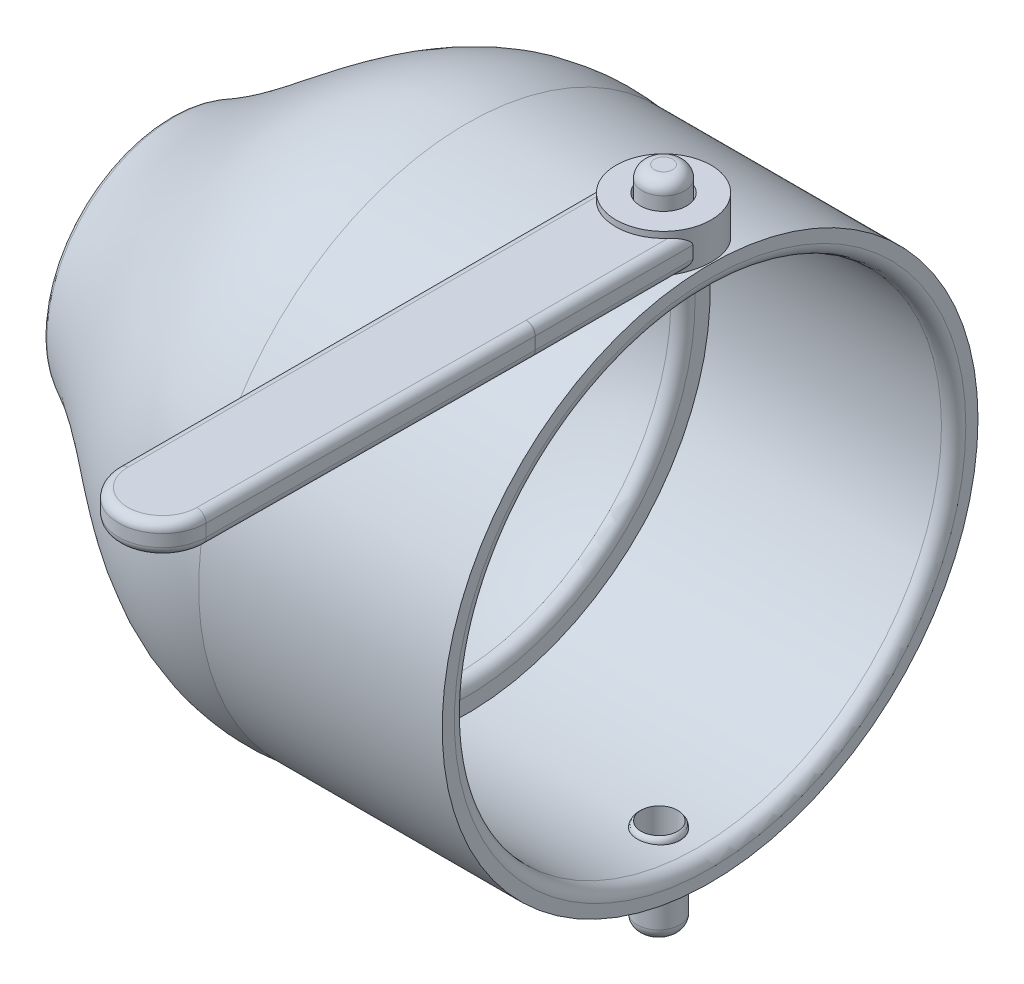
SolidWorks part; units mm, degrees
ref_plane "Front Plane" through (0, 0, 0) normal (0, 0, 1) x (1, 0, 0)
ref_plane "Top Plane" through (0, 0, 0) normal (0, 1, 0) x (1, 0, 0)
ref_plane "Right Plane" through (0, 0, 0) normal (1, 0, 0) x (0, 0, -1)
sketch "Sketch1" plane through (0, 0, 0) normal (1, 0, 0) x (0, 0, -1)
  circle A0 centre (0, 0) radius 22
  dimension "D1" = 44
extrude "Steer controller" add sketch "Sketch1" along normal blind 20
sketch "Sketch2" plane through (0, 0, 0) normal (-1, 0, 0) x (0, 0, 1)
  circle A0 centre (0, 0) radius 20
  dimension "D1" = 40
extrude "Cut-Extrude1" cut sketch "Sketch2" against normal blind 20
ref_plane "plane for top screw" through (0, 22, 0) normal (0, 1, 0) x (1, 0, 0)
sketch "Sketch4" plane through (0, 22, 0) normal (0, 1, 0) x (1, 0, 0)
  line L0 (0, 0) -> (16, 0.1804) construction
  circle A0 centre (16, 0.1804) radius 1.75
  dimension "D1" = 3.5
  dimension "D2" = 16
extrude "Place holder for top screw" add sketch "Sketch4" along normal blind 5 and the other way blind 2.5
ref_plane "Plane for bottom screw" through (0, -22, 0) normal (0, 1, 0) x (1, 0, 0)
sketch "Sketch5" plane through (0, -22, 0) normal (0, 1, 0) x (1, 0, 0)
  line L0 (16, -0.2319) -> (0, 0) construction
  circle A0 centre (16, -0.2319) radius 1.75
  dimension "D2" = 3.5
  dimension "D1" = 16
extrude "Boss-Extrude bottom screw " add sketch "Sketch5" along normal blind 2.5 and the other way blind 5
sketch "Sketch6" plane through (0, 19.5, 0) normal (0, -1, 0) x (1, 0, 0)
  line L0 (16, -0.1804) -> (0, 0) construction
  circle A0 centre (16, -0.1804) radius 1.5
  dimension "D1" = 3
extrude "top screw cut" cut sketch "Sketch6" against normal blind 6.6
fillet "top screw fillet inside" radius 0.3 1 edges at (16, 26.1, -1.6804)
fillet "top screw fillet outside" radius 1 1 edges at (16, 27, 1.5696)
fillet "Fillet3" radius 0.55 1 edges at (16, 19.5, 1.5696)
sketch "Sketch8" plane through (0, -19.5, 0) normal (0, 1, 0) x (1, 0, 0)
  line L0 (0, 0) -> (16, -0.1698) construction
  circle A0 centre (16, -0.1698) radius 1.5
  dimension "D1" = 3
  dimension "D2" = 16
extrude "bottom screw cut" cut sketch "Sketch8" against normal blind 6.6
fillet "bottom srcrew fillet inside" radius 0.3 1 edges at (16, -26.1, 1.6698)
fillet "bottom screw fillet outside" radius 1 1 edges at (16, -27, 1.9819)
fillet "Fillet7" radius 0.55 1 edges at (16, -19.5, 1.9819)
sketch "Sketch9" plane through (0, 22, 0) normal (0, 1, 0) x (1, 0, 0)
  line L0 (0, 0) -> (16, 0.1804) construction
  circle A0 centre (16, 0.1804) radius 1.9
  circle A1 centre (16, 0.1804) radius 3.9
  dimension "D1" = 3.8
  dimension "D2" = 2
extrude "Boss-Extrude14" add sketch "Sketch9" along normal blind 3 and the other way up to surface separate body other way up to face at (15.6041, -21.9506, -1.4728)
ref_plane "Plane for controling the steer" through (0, 22, 0) normal (0, 1, 0) x (1, 0, 0)
sketch "Sketch10" plane through (0, 22, 0) normal (0, 1, 0) x (1, 0, 0)
  line L1 (12.2834, -0.8501) -> (12.2834, -40.8501)
  line L2 (19.4833, -40.877) -> (19.684, -14.0578)
  line L3 (19.6841, -14.0309) -> (19.6841, -1.0149)
  arc A0 (12.2834, -40.8501) -> (19.4833, -40.877) centre (15.8834, -40.8501) ccw
  arc A1 (19.684, -14.0578) -> (19.6841, -14.0309) centre (16.0841, -14.0309) ccw
  spline S0 degree 3 poles (19.6841, -1.0149) (18.7856, -4.1383) (13.6034, -5.1016) (12.2834, -0.8501) knots 0 0 0 0 1 1 1 1
  dimension "D1" = 3.6
  dimension "D2" = 40
extrude "Boss-Extrude steer controller" add sketch "Sketch10" along normal blind 2.5
fillet "steer controller Fillet bottom" radius 0.75 5 edges at (19.6841, 22, 7.565) (19.6841, 22, 14.0444) (19.5837, 22, 27.4674) (15.8699, 22, 44.4501) (12.2834, 22, 20.9258)
fillet "Steer controller Fillet top" radius 0.75 5 edges at (12.2834, 24.5, 20.9258) (15.8699, 24.5, 44.4501) (19.6841, 24.5, 7.565) (19.6841, 24.5, 14.0444) (19.5837, 24.5, 27.4674)
ref_plane "Plane7" through (0, 0, 0) normal (0, 0, 1) x (1, 0, 0)
sketch "Sketch12" plane through (0, 0, 0) normal (0, 0, 1) x (1, 0, 0)
  line L0 (0, 20) -> (0, -20) construction
  line L1 (0, 22) -> (0, -22) construction
  line L2 (0, 0) -> (-56.5954, 0) construction
  line L3 (0, 21.9574) -> (0, 17.7455)
  spline S0 degree 3 poles (0, 21.9574) (-8.5358, 23.1251) (-15.4524, 15.3173) (-25.5078, 9.396) (-29.4793, 8.6247) knots 0 0 0 0 0.540552 0.76614 0.76614 0.76614 0.76614
  spline S1 degree 3 poles (0, 17.7455) (-11.1597, 18.3509) (-17.7494, 6.2896) (-29.4793, 8.6247) knots 0 0 0 0 1 1 1 1
  dimension "D1" = 33.1462
revolve "Revolve1" add sketch "Sketch12" angle 360 about L2
fillet "Fillet11" radius 1 1 edges at (-29.4793, 8.6247, 0)
fillet "Fillet12" radius 1 1 edges at (0, 17.7455, 0)
fillet "Fillet13" radius 1 1 edges at (20, 0, 20)
